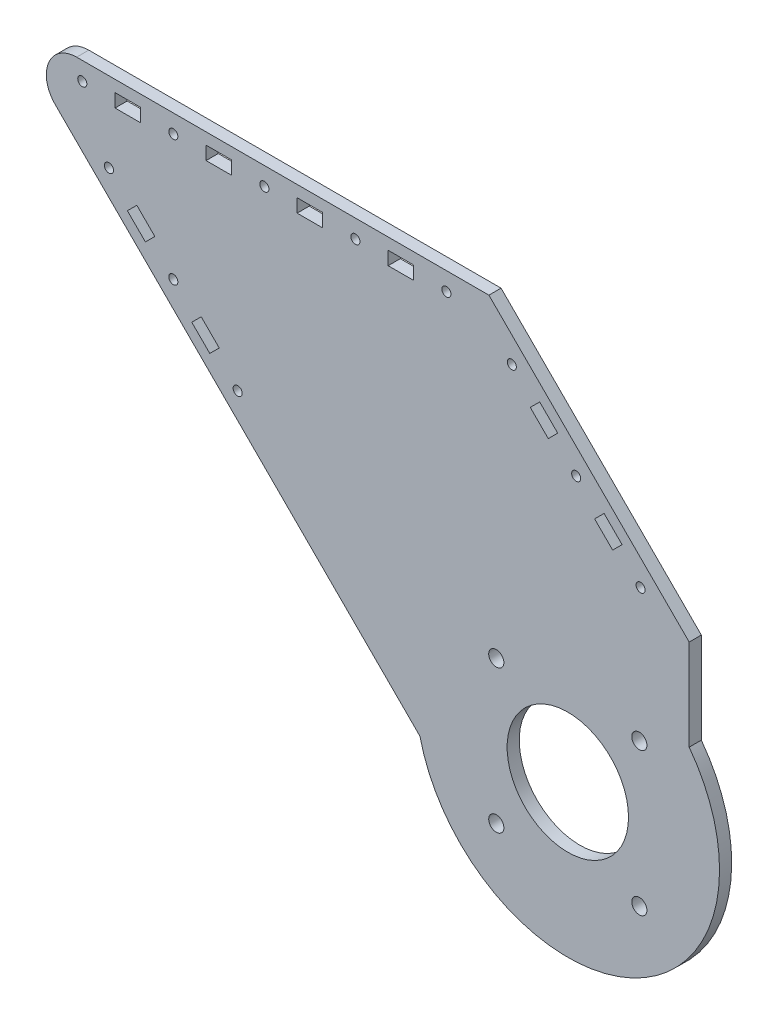
SolidWorks part; units mm, degrees
ref_plane "前视基准面" through (0, 0, 0) normal (0, 0, 1) x (1, 0, 0)
ref_plane "上视基准面" through (0, 0, 0) normal (0, 1, 0) x (1, 0, 0)
ref_plane "右视基准面" through (0, 0, 0) normal (1, 0, 0) x (0, 0, -1)
sketch "草图1" plane through (0, 0, 0) normal (0, 0, 1) x (1, 0, 0)
  line L261 (47.0274, 35.0547) -> (47.0274, 15.0547) construction
  line L315 (-82.9726, 135.0547) -> (-82.9726, 64.5659) construction
  line L316 (-52.9726, 135.0547) -> (-52.9726, 126.7057) construction
  line L332 (-112.9726, 135.0547) -> (-97.9726, 135.0547) construction
  line L334 (-42.1726, 137.2547) -> (-33.7726, 137.2547)
  line L335 (-42.1726, 137.2547) -> (-42.1726, 132.8547)
  line L336 (-42.1726, 132.8547) -> (-33.7726, 132.8547)
  line L337 (-33.7726, 137.2547) -> (-33.7726, 132.8547)
  line L338 (-42.1726, 137.2547) -> (-33.7726, 132.8547) construction
  line L339 (-42.1726, 132.8547) -> (-33.7726, 137.2547) construction
  line L389 (-114.8256, 141.0547) -> (21.0274, 141.0547)
  line L390 (-22.9726, 135.0547) -> (-22.9726, 144.5851) construction
  line L395 (-37.9726, 135.0547) -> (-7.9726, 135.0547) construction
  line L418 (87.0274, 75.0547) -> (21.0274, 141.0547)
  line L419 (-3.7726, 132.8547) -> (-12.1726, 137.2547) construction
  line L420 (-3.7726, 137.2547) -> (-12.1726, 132.8547) construction
  line L421 (7.0274, 135.0547) -> (-7.9726, 135.0547) construction
  line L422 (-12.1726, 137.2547) -> (-12.1726, 132.8547)
  line L423 (-3.7726, 132.8547) -> (-12.1726, 132.8547)
  line L424 (-3.7726, 137.2547) -> (-3.7726, 132.8547)
  line L443 (-3.7726, 137.2547) -> (-12.1726, 137.2547)
  line L444 (-102.1726, 137.2547) -> (-93.7726, 132.8547) construction
  line L445 (-102.1726, 132.8547) -> (-93.7726, 137.2547) construction
  line L446 (7.0274, -4.9037) -> (-121.8956, 123.9827) construction
  line L447 (-67.9726, 135.0547) -> (-97.9726, 135.0547) construction
  line L448 (47.0274, 15.0547) -> (-9.5411, -41.5138) construction
  line L449 (-63.7726, 132.8547) -> (-72.1726, 137.2547) construction
  line L483 (-63.7726, 137.2547) -> (-72.1726, 132.8547) construction
  line L515 (47.0274, 35.0547) -> (47.0274, 135.0547) construction
  line L516 (47.0274, 135.0547) -> (-52.9726, 135.0547) construction
  line L517 (-102.1726, 137.2547) -> (-93.7726, 137.2547)
  line L518 (-102.1726, 137.2547) -> (-102.1726, 132.8547)
  line L519 (-102.1726, 132.8547) -> (-93.7726, 132.8547)
  line L520 (-93.7726, 137.2547) -> (-93.7726, 132.8547)
  line L521 (-72.1726, 137.2547) -> (-72.1726, 132.8547)
  line L522 (-63.7726, 132.8547) -> (-72.1726, 132.8547)
  line L523 (-63.7726, 137.2547) -> (-63.7726, 132.8547)
  line L524 (-63.7726, 137.2547) -> (-72.1726, 137.2547)
  line L551 (7.0274, -4.9037) -> (87.0274, -4.9037) construction
  line L552 (7.0274, -4.9037) -> (7.0274, 75.0547) construction
  line L553 (7.0274, 75.0547) -> (87.0274, 75.0547) construction
  line L554 (87.0274, -4.9037) -> (87.0274, 75.0547) construction
  line L556 (21.4033, 132.1936) -> (81.3921, 72.2048) construction
  line L557 (54.0274, 108.0547) -> (35.0674, 89.0947) construction
  line L558 (43.7037, 113.0045) -> (34.6527, 115.8329) construction
  line L559 (55.8659, 94.6197) -> (61.8056, 88.68)
  line L576 (55.8659, 94.6197) -> (58.9772, 97.731)
  line L577 (58.9772, 97.731) -> (64.9169, 91.7913)
  line L578 (61.8056, 88.68) -> (64.9169, 91.7913)
  line L579 (55.8659, 94.6197) -> (64.9169, 91.7913) construction
  line L580 (58.9772, 97.731) -> (61.8056, 88.68) construction
  line L581 (40.5924, 109.8932) -> (37.764, 118.9442) construction
  line L582 (34.6527, 115.8329) -> (37.764, 118.9442)
  line L583 (43.7037, 113.0045) -> (37.764, 118.9442)
  line L584 (40.5924, 109.8932) -> (43.7037, 113.0045)
  line L585 (40.5924, 109.8932) -> (34.6527, 115.8329)
  line L586 (60.3914, 93.2055) -> (58.8358, 91.6499) construction
  line L587 (39.1782, 114.4187) -> (37.6226, 112.8631) construction
  line L589 (14.0274, 68.0547) -> (9.4285, 72.6537) construction
  line L594 (-122.0988, 132.6698) -> (-32.3261, 42.9227) construction
  line L599 (-82.9726, 93.5547) -> (-61.7564, 72.3446) construction
  line L605 (-25.9633, 28.0776) -> (-21.7212, 32.3208) construction
  line L615 (-73.7793, 87.4749) -> (-76.8901, 84.3632)
  line L616 (-73.7793, 87.4749) -> (-67.8388, 81.5361)
  line L621 (-76.8901, 84.3632) -> (-70.9496, 78.4244)
  line L623 (47.0274, 15.0547) -> (103.596, -41.5138) construction
  line L624 (87.0274, 45.0547) -> (87.0274, 75.0547)
  line L628 (-67.8388, 81.5361) -> (-70.9496, 78.4244)
  line L629 (-73.7793, 87.4749) -> (-70.9496, 78.4244) construction
  line L630 (-76.8901, 84.3632) -> (-67.8388, 81.5361) construction
  line L631 (-82.9726, 93.5547) -> (-87.2146, 89.3115) construction
  line L632 (-89.055, 102.7463) -> (-92.1658, 99.6345)
  line L633 (-94.9955, 108.6851) -> (-98.1064, 105.5734)
  line L634 (-92.1658, 99.6345) -> (-98.1064, 105.5734)
  line L635 (-89.055, 102.7463) -> (-94.9955, 108.6851)
  line L636 (-1.6926, 3.8138) -> (-121.8956, 123.9827)
  circle A39 centre (-52.9726, 135.0547) radius 1.5
  circle A42 centre (47.0274, 15.0547) radius 20
  circle A49 centre (-22.9726, 135.0547) radius 1.5
  circle A69 centre (7.0274, 135.0547) radius 1.5
  circle A92 centre (-112.9726, 135.0547) radius 1.5
  circle A93 centre (-82.9726, 135.0547) radius 1.5
  circle A98 centre (49.7848, 103.8121) radius 1.5
  circle A99 centre (70.998, 82.5989) radius 1.5
  circle A100 centre (28.5716, 125.0253) radius 1.5
  circle A107 centre (70.5974, 38.6247) radius 2.5
  circle A108 centre (70.5974, -8.5153) radius 2.5
  circle A109 centre (23.4574, -8.5153) radius 2.5
  circle A110 centre (23.4574, 38.6247) radius 2.5
  circle A114 centre (-82.9726, 93.5547) radius 1.5
  circle A115 centre (-61.7564, 72.3446) radius 1.5
  circle A116 centre (-104.1888, 114.7649) radius 1.5
  arc A117 (-114.8256, 141.0547) -> (-121.8956, 123.9827) centre (-114.8256, 131.0547) ccw
  circle A118 centre (47.0274, 15.0547) radius 50 construction
  arc A119 (-1.6926, 3.8138) -> (87.0274, 45.0547) centre (47.0274, 15.0547) ccw
  point P5 (210.9534, 218.4629)
  point P6 (288.6284, 218.4629)
  point P54 (-105.4726, 135.0547)
  point P60 (60.3914, 93.2055)
  point P91 (-72.3645, 82.9496)
  dimension "D1" = 40
  dimension "D3" = 40
  dimension "D5" = 23.57
  dimension "D4" = 5
  dimension "D6" = 23.57
  dimension "D2" = 40
  dimension "D7" = 6
  dimension "D12" = 3
  dimension "D22" = 3
  dimension "D8" = 30
  dimension "D28" = 10
  dimension "D9" = 15
  dimension "D10" = 15
  dimension "D11" = 8.4
  dimension "D13" = 4.4
  dimension "D14" = 6
  dimension "D15" = 45
  dimension "D16" = 41.5
  dimension "D17" = 8.4
  dimension "D21" = 6
  dimension "D23" = 15
  dimension "D24" = 8.4
  dimension "D25" = 4.4
  dimension "D26" = 4.4
  dimension "D27" = 4
  dimension "D29" = 45
extrude "凸台-拉伸1" add sketch "草图1" along normal blind 4
sketch "草图2" plane through (0, 0, 0) normal (0, 0, -1) x (-1, 0, 0)
  line L0 (74.5504, 85.1178) -> (32.124, 42.6914) construction
  line L3 (-27.0274, 55.0547) -> (-70.998, 82.5989) construction
  line L5 (-7.0274, 135.0547) -> (112.9726, 135.0547) construction
  line L6 (112.9726, 135.0547) -> (138.9726, 92.2861) construction
  line L8 (74.5504, 85.1178) -> (112.9726, 135.0547) construction
  line L9 (138.9726, 92.2861) -> (90.2039, 92.2861) construction
  line L10 (90.2039, 92.2861) -> (74.5504, 85.1178) construction
  line L11 (98.7922, 103.5057) -> (110.419, 118.6169)
  line L12 (113.7131, 118.4362) -> (122.8995, 103.325)
  line L13 (121.1905, 100.2861) -> (100.3774, 100.2861)
  line L14 (52.4384, 75.7338) -> (-40.5172, 74.1251) construction
  line L15 (112.9726, 135.0547) -> (138.9726, 135.0547) construction
  line L16 (138.9726, 141.0547) -> (138.9726, 92.2861) construction
  line L17 (138.9726, 135.0547) -> (138.9726, 92.2861) construction
  line L21 (127.1982, 127.0547) -> (118.6873, 141.0547)
  line L22 (-21.0274, 141.0547) -> (114.8256, 141.0547) construction
  line L23 (130.9726, 120.8462) -> (138.9726, 107.6866)
  line L24 (96.315, 100.2861) -> (112.1978, 120.9288) construction
  line L25 (112.1978, 120.9288) -> (124.7469, 100.2861) construction
  line L26 (127.1982, 127.0547) -> (130.9726, 120.8462)
  line L27 (130.9726, 127.0547) -> (130.9726, 120.8462) construction
  line L28 (127.1982, 127.0547) -> (130.9726, 127.0547) construction
  line L29 (74.5504, 85.1178) -> (-7.0274, 135.0547) construction
  line L30 (124.7469, 100.2861) -> (96.315, 100.2861) construction
  line L31 (-23.6122, 63.5354) -> (-40.5172, 74.1251) construction
  line L32 (52.4384, 75.7338) -> (29.2014, 52.4968) construction
  line L33 (-23.3319, 117.5371) -> (-48.886, 91.9829) construction
  line L34 (43.4854, 93.5816) -> (-48.886, 91.9829) construction
  line L35 (43.4854, 93.5816) -> (-7.6073, 124.8574) construction
  line L36 (24.9136, 126.0547) -> (94.6921, 126.0547) construction
  line L37 (72.3501, 97.0171) -> (24.9136, 126.0547) construction
  line L38 (73.4463, 98.4417) -> (92.2149, 122.8351)
  line L39 (32.0116, 126.0547) -> (90.6298, 126.0547)
  line L40 (70.817, 97.9555) -> (30.9675, 122.349)
  line L41 (74.5504, 85.1178) -> (-70.998, 82.5989) construction
  line L42 (-7.0274, 135.0547) -> (-28.5716, 125.0253) construction
  line L43 (-28.5716, 125.0253) -> (-70.998, 82.5989) construction
  line L44 (36.6167, 93.4627) -> (-43.9377, 92.0686)
  line L45 (-23.3319, 117.5371) -> (-45.3865, 95.4825)
  line L46 (-7.6073, 124.8574) -> (-23.3319, 117.5371)
  line L47 (37.6263, 97.1682) -> (-7.6073, 124.8574)
  line L48 (32.124, 42.6914) -> (-27.0274, 55.0547) construction
  line L49 (29.2014, 52.4968) -> (-23.6122, 63.5354)
  line L50 (-23.6122, 63.5354) -> (-34.8054, 70.5471)
  line L51 (47.4901, 75.6482) -> (-33.7783, 74.2417)
  line L52 (48.9389, 72.2343) -> (29.2014, 52.4968)
  line L53 (96.315, 100.2861) -> (96.315, 100.2861) construction
  line L54 (72.3501, 97.0171) -> (94.6921, 126.0547) construction
  line L55 (138.9726, 107.6866) -> (138.9726, 141.0547)
  line L56 (138.9726, 141.0547) -> (118.6873, 141.0547)
  arc A2 (110.419, 118.6169) -> (113.7131, 118.4362) centre (112.0041, 117.3973) cw
  arc A3 (98.7922, 103.5057) -> (100.3774, 100.2861) centre (100.3774, 102.2861) ccw
  arc A4 (121.1905, 100.2861) -> (122.8995, 103.325) centre (121.1905, 102.2861) ccw
  arc A6 (-33.7783, 74.2417) -> (-34.8054, 70.5471) centre (-33.7437, 72.242) ccw
  arc A7 (47.4901, 75.6482) -> (48.9389, 72.2343) centre (47.5247, 73.6485) cw
  arc A8 (-45.3865, 95.4825) -> (-43.9377, 92.0686) centre (-43.9723, 94.0683) ccw
  arc A9 (36.6167, 93.4627) -> (37.6263, 97.1682) centre (36.5821, 95.4624) ccw
  arc A10 (32.0116, 126.0547) -> (30.9675, 122.349) centre (32.0116, 124.0547) ccw
  arc A11 (90.6298, 126.0547) -> (92.2149, 122.8351) centre (90.6298, 124.0547) cw
  arc A12 (70.817, 97.9555) -> (73.4463, 98.4417) centre (71.8612, 99.6613) ccw
  dimension "D1" = 8
  dimension "D2" = 8
  dimension "D3" = 9
  dimension "D4" = 9
  dimension "D5" = 9
extrude "切除-拉伸1" [suppressed] cut sketch "草图2" against normal blind 10
